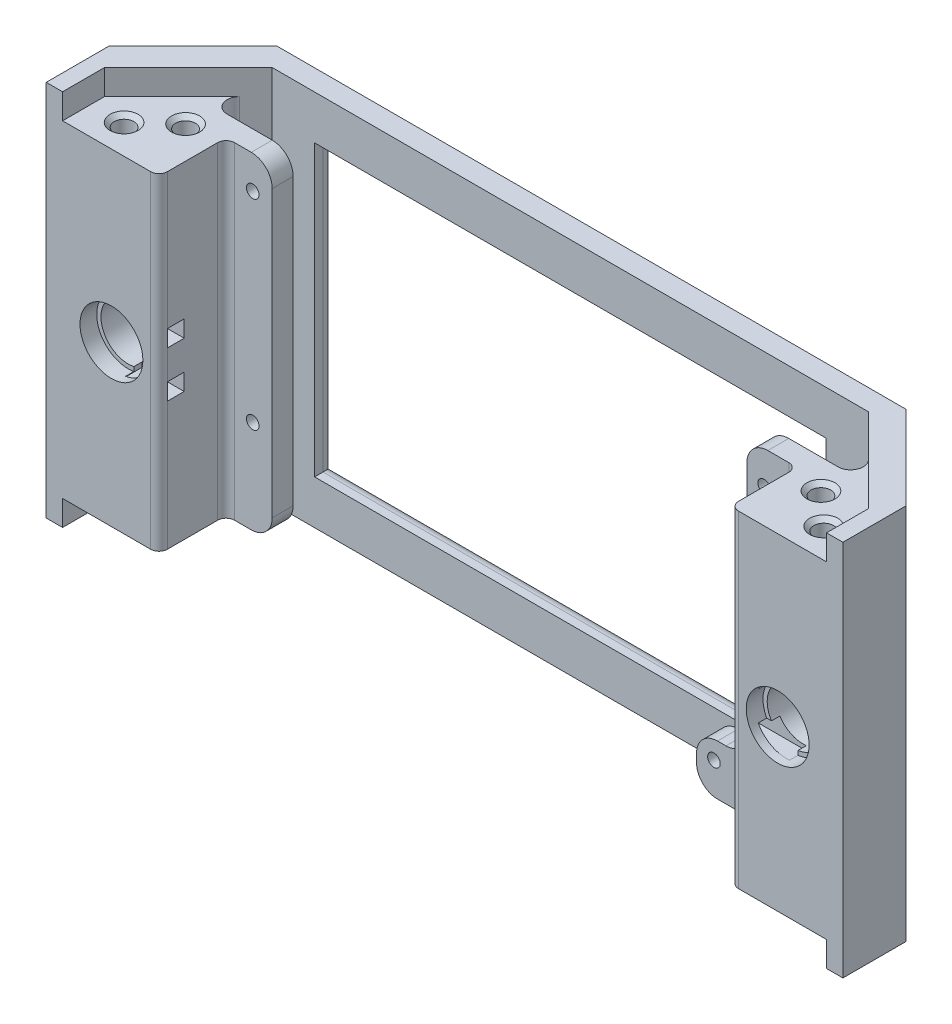
SolidWorks part; units mm, degrees
ref_plane "Front Plane" through (0, 0, 0) normal (0, 0, 1) x (1, 0, 0)
ref_plane "Top Plane" through (0, 0, 0) normal (0, 1, 0) x (1, 0, 0)
ref_plane "Right Plane" through (0, 0, 0) normal (1, 0, 0) x (0, 0, -1)
sketch "Sketch1" plane through (0, 0, 0) normal (0, 0, 1) x (1, 0, 0)
  line L1 (-95, 45) -> (95, 45)
  line L2 (-95, 45) -> (-95, -45)
  line L3 (-95, -45) -> (95, -45)
  line L4 (95, 45) -> (95, -45)
  line L5 (-95, 45) -> (95, -45) construction
  line L6 (-95, -45) -> (95, 45) construction
  line L7 (-61, 34.5) -> (61, 34.5)
  line L8 (-61, 34.5) -> (-61, -34.5)
  line L9 (-61, -34.5) -> (61, -34.5)
  line L10 (61, 34.5) -> (61, -34.5)
  line L11 (-61, 34.5) -> (61, -34.5) construction
  line L12 (-61, -34.5) -> (61, 34.5) construction
  point P0 (0, 0)
  point P6 (0, 0)
  dimension "D1" = 122
  dimension "D2" = 190
  dimension "D3" = 69
  dimension "D4" = 90
extrude "Boss-Extrude1" add sketch "Sketch1" along normal blind 5
sketch "Sketch2" plane through (0, 0, 5) normal (0, 0, 1) x (1, 0, 0)
  line L0 (-95, -45) -> (95, -45) construction
  line L1 (-95, 45) -> (-91.1, 45)
  line L2 (-95, 45) -> (-95, -45)
  line L3 (-95, -45) -> (-91.1, -45)
  line L4 (-91.1, 45) -> (-91.1, -45)
  line L5 (0, 0) -> (0, 45) construction
  line L6 (95, 45) -> (-95, 45) construction
  line L7 (95, -45) -> (91.1, -45)
  line L8 (91.1, 45) -> (91.1, -45)
  line L9 (95, 45) -> (91.1, 45)
  line L10 (95, 45) -> (95, -45)
  dimension "D1" = 3.9
extrude "Boss-Extrude2" add sketch "Sketch2" along normal blind 30
sketch "Sketch3" plane through (0, 45, 0) normal (0, 1, 0) x (1, 0, 0)
  line L0 (-91.1, -35) -> (-91.1, -5) construction
  line L1 (-91.1, -14) -> (-57.1, -14)
  line L2 (-91.1, -14) -> (-91.1, -19)
  line L3 (-91.1, -19) -> (-57.1, -19)
  line L4 (-57.1, -14) -> (-57.1, -19)
  line L5 (91.1, -35) -> (91.1, -5) construction
  line L6 (91.1, -14) -> (44.1, -14)
  line L7 (91.1, -14) -> (91.1, -19)
  line L8 (91.1, -19) -> (44.1, -19)
  line L9 (44.1, -14) -> (44.1, -19)
  line L10 (91.1, -5) -> (-91.1, -5) construction
  dimension "D1" = 9
  dimension "D2" = 9
  dimension "D3" = 5
  dimension "D4" = 5
  dimension "D5" = 34
  dimension "D6" = 47
extrude "Boss-Extrude3" add sketch "Sketch3" against normal up to surface (90 mm away) up to face at (0, -45, 18.75)
sketch "Sketch4" plane through (0, 0, 19) normal (0, 0, 1) x (1, 0, 0)
  line L0 (91.1, -45) -> (91.1, 45) construction
  line L1 (-91.1, 45) -> (91.1, 45)
  line L2 (-91.1, 45) -> (-91.1, 39)
  line L3 (-91.1, 39) -> (91.1, 39)
  line L4 (91.1, 45) -> (91.1, 39)
  line L5 (0, 0) -> (-91.1, 0) construction
  line L6 (-91.1, -45) -> (-91.1, 45) construction
  line L7 (-91.1, -39) -> (91.1, -39)
  line L8 (91.1, -45) -> (91.1, -39)
  line L9 (-91.1, -45) -> (91.1, -45)
  line L10 (-91.1, -45) -> (-91.1, -39)
  dimension "D1" = 6
extrude "Cut-Extrude1" cut sketch "Sketch4" against normal blind 5
sketch "Sketch5" plane through (0, 0, 19) normal (0, 0, 1) x (1, 0, 0)
  line L0 (0, 0) -> (-61.75, 0) construction
  line L1 (-70.2, 37.38) -> (70.2, 37.38) construction
  line L2 (-70.2, 37.38) -> (-70.2, -37.38) construction
  line L3 (-70.2, -37.38) -> (70.2, -37.38) construction
  line L4 (70.2, 37.38) -> (70.2, -37.38) construction
  line L5 (-70.2, 37.38) -> (70.2, -37.38) construction
  line L6 (-70.2, -37.38) -> (70.2, 37.38) construction
  line L7 (-61.75, 0) -> (-61.75, 31.13) construction
  line L8 (-61.75, 0) -> (-61.75, -16.61) construction
  line L9 (48.25, 0) -> (60.23, 0) construction
  line L10 (60.23, 0) -> (60.23, 31.13) construction
  line L11 (0, 0) -> (48.25, 0) construction
  line L12 (48.25, 0) -> (48.25, -31.38) construction
  circle A0 centre (-61.75, 31.13) radius 1.5
  circle A1 centre (-61.75, -16.61) radius 1.5
  circle A2 centre (60.23, 31.13) radius 1.5
  circle A3 centre (48.25, -31.38) radius 1.5
  point P0 (0, 0)
  dimension "D10" = 3
  dimension "D11" = 3
  dimension "D12" = 3
  dimension "D13" = 3
  dimension "D1" = 140.4
  dimension "D2" = 74.76
  dimension "D3" = 61.75
  dimension "D4" = 31.13
  dimension "D5" = 16.61
  dimension "D6" = 60.23
  dimension "D7" = 31.13
  dimension "D8" = 48.25
  dimension "D9" = 31.38
extrude "Cut-Extrude2" cut sketch "Sketch5" against normal up to surface (5 mm away) up to face at (67.6, 0, 14)
sketch "Sketch6" plane through (0, 0, 19) normal (0, 0, 1) x (1, 0, 0)
  line L1 (44.1, 39) -> (56.1, 39)
  line L2 (44.1, 39) -> (44.1, -27)
  line L3 (44.1, -27) -> (56.1, -27)
  line L4 (56.1, 39) -> (56.1, -27)
  dimension "D1" = 12
  dimension "D2" = 66
extrude "Cut-Extrude3" cut sketch "Sketch6" against normal up to surface (5 mm away) up to face at (46.75, -31.38, 14)
fillet "Fillet3" radius 3 4 edges at (-61, 0, 0) (0, -34.5, 0) (61, 0, 0) (0, 34.5, 0)
chamfer "Chamfer6" distance 20 angle 45 4 edges at (91.1, 0, 5) (95, 0, 0) (-95, 0, 0) (-91.1, 0, 5)
sketch "Sketch7" plane through (0, 39, 0) normal (0, 1, 0) x (1, 0, 0)
  line L0 (-85.1, -19) -> (-91.1, -25)
  line L1 (-91.1, -25) -> (-91.1, -35)
  line L2 (-91.1, -35) -> (-68.1, -35)
  line L3 (-68.1, -35) -> (-68.1, -19)
  line L4 (-85.1, -19) -> (-57.1, -19) construction
  line L5 (-68.1, -19) -> (-85.1, -19)
  line L6 (0, 0) -> (0, -5) construction
  line L7 (71.1, -5) -> (-71.1, -5) construction
  line L8 (68.1, -35) -> (68.1, -19)
  line L9 (91.1, -35) -> (68.1, -35)
  line L10 (91.1, -25) -> (91.1, -35)
  line L11 (85.1, -19) -> (91.1, -25)
  line L12 (68.1, -19) -> (85.1, -19)
  dimension "D1" = 23
extrude "Boss-Extrude4" add sketch "Sketch7" against normal up to surface (78 mm away) up to face at (-69.85, -39, 16.5)
fillet "Fillet4" radius 5 6 edges at (-57.1, -39, 16.5) (-57.1, 39, 16.5) (56.1, 39, 16.5) (44.1, -39, 16.5) (44.1, -27, 16.5) (56.1, -27, 16.5)
fillet "Fillet5" radius 2 4 edges at (-68.1, 0, 35) (68.1, 0, 35) (68.1, 0, 19) (-68.1, 0, 19)
fillet "Fillet6" radius 3 2 edges at (-80.1, 0, 14) (80.1, 0, 14)
sketch "Sketch9" plane through (0, 0, 35) normal (0, 0, 1) x (1, 0, 0)
  line L6 (0, 0) -> (0, -45) construction
  line L7 (-71.1, -45) -> (71.1, -45) construction
  line L8 (-95, 45) -> (-95, -45) construction
  line L9 (-95, 39) -> (-79.45, 39) construction
  line L10 (-95, 39) -> (-95, -0.9074) construction
  line L11 (-95, -0.9074) -> (-79.45, -0.9074) construction
  line L12 (-79.45, 39) -> (-79.45, -0.9074) construction
  line L13 (-91.1, 39) -> (-70.1, 39) construction
  circle A0 centre (-79.45, -0.9074) radius 6.5
  circle A1 centre (79.45, -0.9074) radius 6.5
  dimension "D3" = 13
  dimension "D1" = 39.9074
  dimension "D2" = 15.55
extrude "Cut-Extrude4" cut sketch "Sketch9" against normal blind 10
sketch "Sketch10" plane through (0, 0, 35) normal (0, 0, 1) x (1, 0, 0)
  circle A0 centre (-79.45, -0.9074) radius 7.5
  circle A1 centre (79.45, -0.9074) radius 7.5
  dimension "D1" = 15
  dimension "D2" = 15
extrude "Cut-Extrude5" cut sketch "Sketch10" against normal blind 4
sketch "Sketch12" plane through (-68.1, 0, 0) normal (1, 0, 0) x (0, 0, -1)
  line L0 (-33, -4.4074) -> (-29, -4.4074)
  line L1 (-33, 39) -> (-23, 39) construction
  line L2 (-33, 39) -> (-33, -0.9074) construction
  line L3 (-33, -0.9074) -> (-23, -0.9074) construction
  line L4 (-23, 39) -> (-23, -0.9074) construction
  line L5 (-33, 6.5926) -> (-23, 6.5926) construction
  line L6 (-33, 6.5926) -> (-33, -8.4074) construction
  line L7 (-33, -8.4074) -> (-23, -8.4074) construction
  line L8 (-23, 6.5926) -> (-23, -8.4074) construction
  line L9 (-33, 6.5926) -> (-23, -8.4074) construction
  line L10 (-33, -8.4074) -> (-23, 6.5926) construction
  line L11 (-33, 6.5926) -> (-29, 6.5926)
  line L12 (-33, 6.5926) -> (-33, 2.5926)
  line L13 (-33, 2.5926) -> (-29, 2.5926)
  line L14 (-29, 6.5926) -> (-29, 2.5926)
  line L15 (-29, -8.4074) -> (-29, -4.4074)
  line L16 (-33, -8.4074) -> (-29, -8.4074)
  line L17 (-33, -8.4074) -> (-33, -4.4074)
  point P5 (-28, -0.9074)
  dimension "D1" = 39.9074
  dimension "D2" = 10
  dimension "D3" = 15
  dimension "D4" = 10
  dimension "D5" = 4
  dimension "D6" = 4
extrude "Cut-Extrude6" cut sketch "Sketch12" against normal blind 10 and the other way blind 148.4
sketch "Sketch15" plane through (0, 39, 0) normal (0, 1, 0) x (1, 0, 0)
  line L0 (68.1, -21) -> (68.1, -33) construction
  line L5 (72.8574, -14) -> (61.1, -14) construction
  line L6 (91.1, -35) -> (68.1, -35) construction
  line L7 (91.1, -35) -> (91.1, -14) construction
  line L8 (91.1, -14) -> (68.1, -14) construction
  line L9 (68.1, -35) -> (68.1, -14) construction
  line L10 (68.1, -14) -> (75.7667, -21) construction
  line L11 (75.7667, -21) -> (83.4333, -28) construction
  line L12 (83.4333, -28) -> (91.1, -35) construction
  line L13 (0, 0) -> (0, -5) construction
  line L14 (71.1, -5) -> (-71.1, -5) construction
  circle A0 centre (75.7667, -21) radius 2.35
  circle A1 centre (83.4333, -28) radius 2.35
  circle A2 centre (-75.7667, -21) radius 2.35
  circle A3 centre (-83.4333, -28) radius 2.35
  dimension "D1" = 4.7
  dimension "D2" = 4.7
  dimension "D3" = 23
  dimension "D4" = 21
extrude "Cut-Extrude7" cut sketch "Sketch15" against normal blind 8
chamfer "Chamfer7" distance 1 angle 45 4 edges at (-83.4333, 39, 25.65) (-75.7667, 39, 18.65) (83.4333, 39, 30.35) (75.7667, 39, 23.35)
sketch "Sketch17" plane through (0, -39, 0) normal (0, -1, 0) x (1, 0, 0)
  line L0 (0, 0) -> (0, 5) construction
  line L1 (91.1, 35) -> (68.1, 35) construction
  line L2 (91.1, 35) -> (91.1, 19) construction
  line L3 (91.1, 19) -> (68.1, 19) construction
  line L4 (68.1, 35) -> (68.1, 19) construction
  line L5 (-71.1, 5) -> (71.1, 5) construction
  line L6 (68.1, 33) -> (68.1, 21) construction
  line L7 (66.1, 19) -> (49.1, 19) construction
  circle A0 centre (79.6, 27) radius 6.1
  circle A1 centre (-79.6, 27) radius 6.1
  dimension "D2" = 12.2
  dimension "D1" = 11.5
  dimension "D3" = 8
extrude "Cut-Extrude8" cut sketch "Sketch17" against normal blind 3.2
fillet "Fillet7" radius 0.2 2 edges at (-85.7, -39, 27) (85.7, -39, 27)
